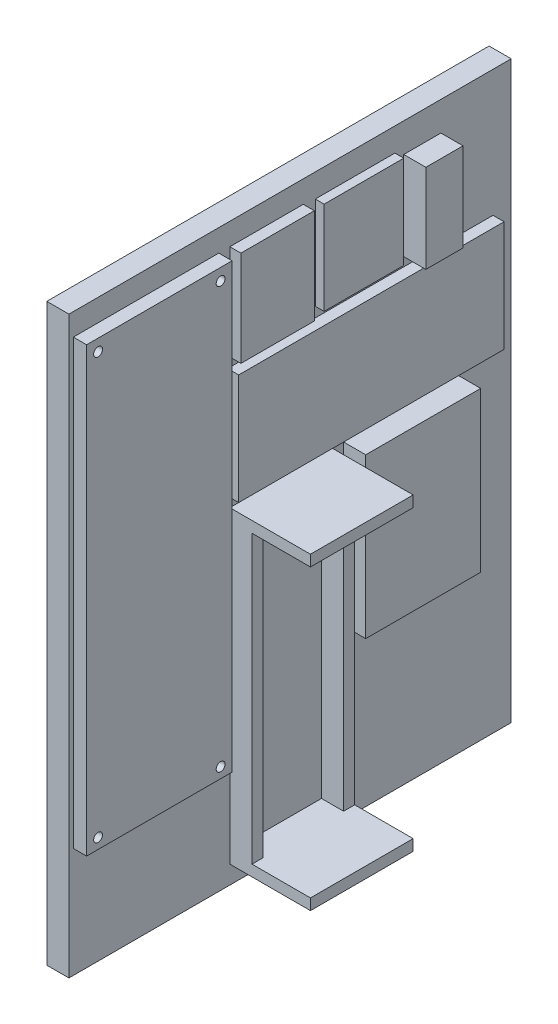
SolidWorks part; units mm, degrees
material "1060 Alloy"
ref_plane "Front Plane" through (0, 0, 0) normal (0, 0, 1) x (1, 0, 0)
ref_plane "Top Plane" through (0, 0, 0) normal (0, 1, 0) x (1, 0, 0)
ref_plane "Right Plane" through (0, 0, 0) normal (1, 0, 0) x (0, 0, -1)
sketch "Sketch1" plane through (0, 0, 0) normal (1, 0, 0) x (0, 0, -1)
  line L1 (-16.445, 50.065) -> (16.445, 50.065)
  line L2 (-16.445, 50.065) -> (-16.445, -50.065)
  line L3 (-16.445, -50.065) -> (16.445, -50.065)
  line L4 (16.445, 50.065) -> (16.445, -50.065)
  line L5 (-17.445, 55.065) -> (82.555, 55.065)
  line L6 (-17.445, 55.065) -> (-17.445, -74.935)
  line L7 (-17.445, -74.935) -> (82.555, -74.935)
  line L8 (82.555, 55.065) -> (82.555, -74.935)
  circle A0 centre (-13.855, 47.395) radius 1
  circle A4 centre (13.855, 47.395) radius 1
  circle A5 centre (13.855, -47.705) radius 1
  circle A6 centre (-13.855, -47.705) radius 1
  dimension "D3" = 2
  dimension "D4" = 2.67
  dimension "D8" = 2
  dimension "D11" = 2
  dimension "D12" = 2
  dimension "D15" = 2.36
  dimension "D1" = 32.89
  dimension "D2" = 100.13
  dimension "D5" = 2.59
  dimension "D6" = 50.065
  dimension "D7" = 16.445
  dimension "D9" = 2.59
  dimension "D10" = 2.67
  dimension "D13" = 2.59
  dimension "D14" = 2.36
  dimension "D16" = 2.59
  dimension "D17" = 95.1
  dimension "D18" = 130
  dimension "D19" = 100
  dimension "D20" = 5
  dimension "D21" = 1
extrude "Boss-Extrude1" add sketch "Sketch1" along normal blind 5 contours L4 L1 L2 L3 A6 A5 A4 A0 | L8 L5 L6 L7 L1 L4 L3 L2 region at (0, 0.0006, 0) region at (0, -13.3057, -43.6002)
sketch "Sketch3" plane through (5, 0, 0) normal (1, 0, 0) x (0, 0, -1)
  line L1 (-16.445, 50.065) -> (16.445, 50.065)
  line L2 (-16.445, 50.065) -> (-16.445, -50.065)
  line L3 (-16.445, -50.065) -> (16.445, -50.065)
  line L4 (16.445, 50.065) -> (16.445, -50.065)
  circle A0 centre (-13.855, 47.395) radius 1 construction
  circle A1 centre (13.855, 47.395) radius 1 construction
  circle A2 centre (13.855, -47.705) radius 1 construction
  circle A3 centre (-13.855, 47.395) radius 1
  circle A4 centre (13.855, 47.395) radius 1
  circle A5 centre (13.855, -47.705) radius 1
  circle A6 centre (-13.855, -47.705) radius 1
  dimension "D5" = 2
  dimension "D6" = 2.36
  dimension "D1" = 2.59
  dimension "D2" = 2.59
  dimension "D3" = 2.67
  dimension "D4" = 2.36
  dimension "D7" = 2.59
extrude "Boss-Extrude3" add sketch "Sketch3" along normal blind 3
sketch "Sketch4" plane through (5, 0, 0) normal (1, 0, 0) x (0, 0, -1)
  line L1 (18.945, 50.065) -> (35.545, 50.065)
  line L2 (18.945, 50.065) -> (18.945, 28.465)
  line L3 (18.945, 28.465) -> (35.545, 28.465)
  line L4 (35.545, 50.065) -> (35.545, 28.465)
  line L10 (16.445, -50.065) -> (16.445, 50.065) construction
  line L11 (16.445, 50.065) -> (-16.445, 50.065) construction
  point P4 (35.545, 39.265)
  point P7 (0, 50.065)
  dimension "D1" = 16.6
  dimension "D2" = 21.6
  dimension "D3" = 0
  dimension "D6" = 2.5
extrude "Boss-Extrude4" add sketch "Sketch4" along normal blind 2.5
sketch "Sketch5" plane through (5, 0, 0) normal (1, 0, 0) x (0, 0, -1)
  line L1 (18.445, 26.465) -> (78.445, 26.465)
  line L2 (18.445, 26.465) -> (18.445, 1.465)
  line L3 (18.445, 1.465) -> (78.445, 1.465)
  line L4 (78.445, 26.465) -> (78.445, 1.465)
  line L5 (18.945, 28.465) -> (35.545, 28.465) construction
  line L6 (16.445, -50.065) -> (16.445, 50.065) construction
  dimension "D1" = 60
  dimension "D2" = 25
  dimension "D3" = 2
  dimension "D4" = 2
extrude "Boss-Extrude5" add sketch "Sketch5" along normal blind 2.5
sketch "Sketch6" plane through (5, 0, 0) normal (1, 0, 0) x (0, 0, -1)
  line L1 (38.2605, 49.7462) -> (56.2605, 49.7462)
  line L2 (38.2605, 49.7462) -> (38.2605, 28.7462)
  line L3 (38.2605, 28.7462) -> (56.2605, 28.7462)
  line L4 (56.2605, 49.7462) -> (56.2605, 28.7462)
  dimension "D1" = 18
  dimension "D2" = 21
extrude "Boss-Extrude6" add sketch "Sketch6" along normal blind 2
sketch "Sketch7" plane through (5, 0, 0) normal (1, 0, 0) x (0, 0, -1)
  line L0 (56.2605, 28.7462) -> (56.2605, 49.7462) construction
  line L1 (58.2605, 48.465) -> (66.6605, 48.465)
  line L2 (58.2605, 48.465) -> (58.2605, 28.465)
  line L3 (58.2605, 28.465) -> (66.6605, 28.465)
  line L4 (66.6605, 48.465) -> (66.6605, 28.465)
  line L5 (78.445, 26.465) -> (18.445, 26.465) construction
  dimension "D1" = 8.4
  dimension "D2" = 20
  dimension "D3" = 2
  dimension "D4" = 2
extrude "Boss-Extrude7" add sketch "Sketch7" along normal blind 5
sketch "Sketch9" plane through (5, 0, 0) normal (1, 0, 0) x (0, 0, -1)
  line L0 (18.445, 1.465) -> (78.445, 1.465) construction
  line L1 (21.445, -3.535) -> (39.665, -3.535)
  line L2 (21.445, -3.535) -> (21.445, -68.335)
  line L3 (21.445, -68.335) -> (39.665, -68.335)
  line L4 (39.665, -3.535) -> (39.665, -68.335)
  line L5 (16.445, -50.065) -> (16.445, 50.065) construction
  line L7 (21.445, -3.535) -> (18.945, -3.535)
  line L8 (21.445, -3.535) -> (21.445, -68.335)
  line L9 (21.445, -68.335) -> (18.945, -68.335)
  line L10 (18.945, -3.535) -> (18.945, -68.335)
  line L11 (39.665, -3.535) -> (42.165, -3.535)
  line L12 (39.665, -3.535) -> (39.665, -68.335)
  line L13 (39.665, -68.335) -> (42.165, -68.335)
  line L14 (42.165, -3.535) -> (42.165, -68.335)
  line L15 (18.945, -68.335) -> (42.165, -68.335)
  line L19 (42.165, -3.535) -> (18.945, -3.535)
  dimension "D1" = 18.22
  dimension "D2" = 64.8
  dimension "D3" = 5
  dimension "D4" = 5
  dimension "D5" = 2.5
  dimension "D6" = 2.5
extrude "Boss-Extrude8" add sketch "Sketch9" along normal blind 5 contours L7 L10 L9 L2 | L14 L11 L4 L13 region at (5, -35.935, -20.195) region at (5, -35.935, -40.915)
sketch "Sketch10" plane through (5, 0, 0) normal (1, 0, 0) x (0, 0, -1)
  line L1 (18.945, -68.335) -> (42.165, -68.335)
  line L2 (18.945, -68.335) -> (18.945, -70.835)
  line L3 (18.945, -70.835) -> (42.165, -70.835)
  line L4 (42.165, -68.335) -> (42.165, -70.835)
  line L5 (18.945, -3.535) -> (42.165, -3.535)
  line L6 (18.945, -3.535) -> (18.945, -1.035)
  line L7 (18.945, -1.035) -> (42.165, -1.035)
  line L8 (42.165, -3.535) -> (42.165, -1.035)
  dimension "D1" = 2.5
  dimension "D2" = 2.5
extrude "Boss-Extrude9" add sketch "Sketch10" along normal blind 18.22
sketch "Sketch11" plane through (5, 0, 0) normal (1, 0, 0) x (0, 0, -1)
  line L0 (42.165, -3.535) -> (42.165, -68.335) construction
  line L1 (44.665, -1.035) -> (70.665, -1.035)
  line L2 (44.665, -1.035) -> (44.665, -37.035)
  line L3 (44.665, -37.035) -> (70.665, -37.035)
  line L4 (70.665, -1.035) -> (70.665, -37.035)
  line L5 (18.445, 1.465) -> (78.445, 1.465) construction
  dimension "D1" = 2.5
  dimension "D2" = 2.5
  dimension "D3" = 36
  dimension "D4" = 26
sketch "Sketch12" plane through (5, 0, 0) normal (1, 0, 0) x (0, 0, -1)
  line L0 (42.165, -3.535) -> (42.165, -68.335) construction
  line L1 (44.665, -1.035) -> (70.665, -1.035)
  line L2 (44.665, -1.035) -> (44.665, -37.035)
  line L3 (44.665, -37.035) -> (70.665, -37.035)
  line L4 (70.665, -1.035) -> (70.665, -37.035)
  line L5 (18.445, 1.465) -> (78.445, 1.465) construction
  dimension "D1" = 2.5
  dimension "2.5" = 2.5
  dimension "D2" = 36
  dimension "D3" = 26
extrude "Boss-Extrude11" add sketch "Sketch12" along normal blind 5 contours L2 L1 L4 L3
extrude "Boss-Extrude10" add sketch "Sketch11" along normal blind 5
